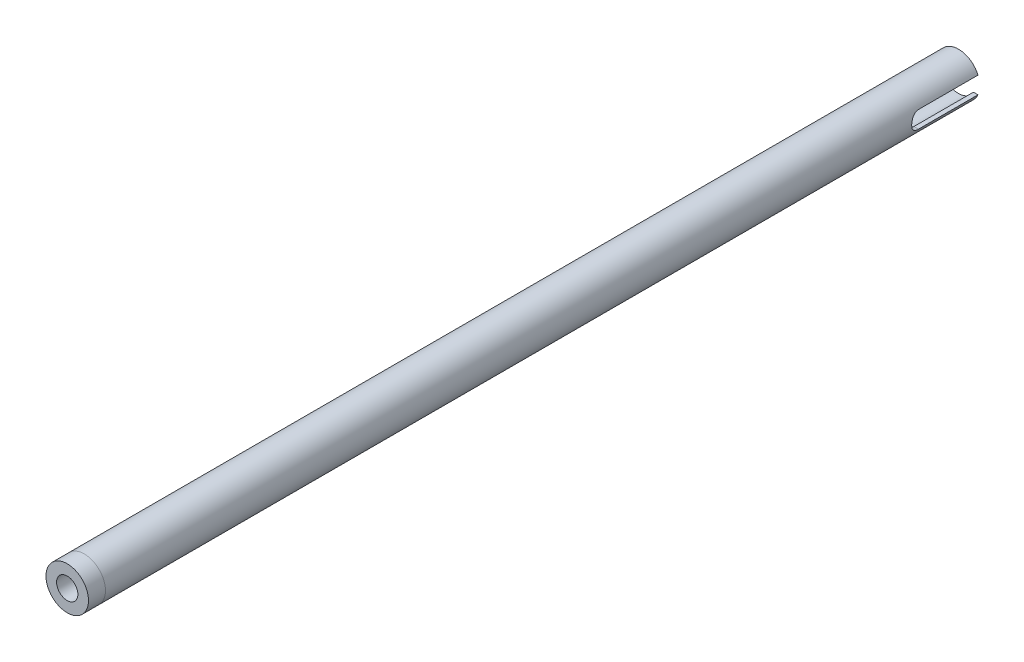
SolidWorks part; units mm, degrees
ref_plane "Front Plane" through (0, 0, 0) normal (0, 0, 1) x (1, 0, 0)
ref_plane "Top Plane" through (0, 0, 0) normal (0, 1, 0) x (1, 0, 0)
ref_plane "Right Plane" through (0, 0, 0) normal (1, 0, 0) x (0, 0, -1)
sketch "Axis" plane through (0, 0, 0) normal (0, 1, 0) x (1, 0, 0)
  line L0 (0, 0) -> (0, 332.6562) construction
  line L1 (0, 0) -> (0, -28.575) construction
  line L2 (0, 332.6562) -> (-7.9375, 332.6562) construction
  line L3 (0, 361.4076) -> (-10.3187, 324.0308) construction
  dimension "D1" = 28.575
  dimension "D2" = 7.9375
sketch "Sketch1" plane through (0, 0, 0) normal (0, 0, 1) x (1, 0, 0)
  line L0 (-7.9375, 0) -> (7.9375, 0) construction
  line L1 (-7.2748, 3.175) -> (7.2748, 3.175)
  line L2 (-7.2748, -3.175) -> (7.2748, -3.175)
  circle A0 centre (0, 0) radius 7.9375
  circle A1 centre (0, 0) radius 6.4135
  circle A2 centre (0, 0) radius 3.9688
  dimension "D1" = 15.875
  dimension "D3" = 7.9375
  dimension "D2" = 1.524
  dimension "D4" = 6.35
extrude "Threaded insert 1-1" add sketch "Sketch1" against normal blind 6.35 contours A2 L1 A1 | A1 L1 A0 | A2 L0 A1 L1 | A1 L0 A0 L1 | L0 A1 L2 A0 | L0 A2 L2 A1 | A2 L2 A1 | A1 L2 A0 | L0 A1 L2 A2 | L0 A0 L2 A1 | A0 L0 A1 L1 | A1 L0 A2 L1 region at (4.7887, 1.6543, 0) region at (4.7887, -1.6543, 0) region at (6.9234, 1.6163, 0) region at (6.9234, -1.6163, 0) region at (-4.7887, -1.6543, 0) region at (-4.7887, 1.6543, 0) region at (0, 4.6159, 0) region at (0, -4.6159, 0) region at (0, 6.5666, 0) region at (6.4237, -3.3281, 0) region at (-6.9234, -1.6163, 0) region at (-6.9234, 1.6163, 0)
extrude "Threaded insert 1-2" add sketch "Sketch1<3>" against normal blind 9.525 from surface contours A2 L1 A1 | A2 L0 A1 L1 | L0 A2 L2 A1 | A2 L2 A1 | L0 A1 L2 A2 | A1 L0 A2 L1 region at (4.7887, 1.6543, 0) region at (4.7887, -1.6543, 0) region at (-4.7887, -1.6543, 0) region at (-4.7887, 1.6543, 0) region at (0, 4.6159, 0) region at (0, -4.6159, 0) starting at face at (7.9375, 0, -6.35)
sketch "Sketch1<3>" plane through (0, 0, 0) normal (0, 0, 1) x (1, 0, 0) same geometry as "Sketch1"
extrude "A-arm tube" add sketch "Sketch1<4>" against normal up to vertex (332.6562 mm away) from surface separate body contours A1 L1 A0 | A1 L0 A0 L1 | L0 A1 L2 A0 | A1 L2 A0 | L0 A0 L2 A1 | A0 L0 A1 L1 region at (6.9234, 1.6163, 0) region at (6.9234, -1.6163, 0) region at (0, 6.5666, 0) region at (6.4237, -3.3281, 0) region at (-6.9234, -1.6163, 0) region at (-6.9234, 1.6163, 0) up to point (0, 0, -332.6562) starting at face at (6.4135, 0, -6.35)
sketch "Sketch1<4>" plane through (0, 0, 0) normal (0, 0, 1) x (1, 0, 0) same geometry as "Sketch1"
extrude "Apex slot" cut sketch "Sketch1<5>" along normal blind 25.4 from surface contours A0 L0 A1 L1 | L0 A0 L2 A1 | A1 L0 A0 L1 | L0 A1 L2 A0 region at (6.9234, 1.6163, 0) region at (6.9234, -1.6163, 0) region at (-6.9234, -1.6163, 0) region at (-6.9234, 1.6163, 0) starting at face at (6.4135, 0, -332.6562)
sketch "Sketch1<5>" plane through (0, 0, 0) normal (0, 0, 1) x (1, 0, 0) same geometry as "Sketch1"
fillet "Fillet1" radius 3.175 4 edges at (-6.4237, 3.175, -307.2562) (-6.4237, -3.175, -307.2562) (6.4237, -3.175, -307.2562) (6.4237, 3.175, -307.2562)
equation "\"tube diameter\"= 5 / 8"
equation "\"tube thickness\"= .06"
equation "\"apex thickness\"= .25"
equation "\"tube slot\"= 1"
equation "\"D1@Sketch1\"=\"tube diameter\""
equation "\"D2@Sketch1\"=\"tube thickness\""
equation "\"threaded insert hole\"= .3125"
equation "\"D3@Sketch1\"=\"threaded insert hole\""
equation "\"D4@Sketch1\"=\"apex thickness\""
equation "\"D1@Apex slot\" = \"tube slot\""
equation "\"D1@Fillet1\"=\"apex thickness\"/2"
equation "\"D2@Axis\"=\"tube diameter\"/2"
